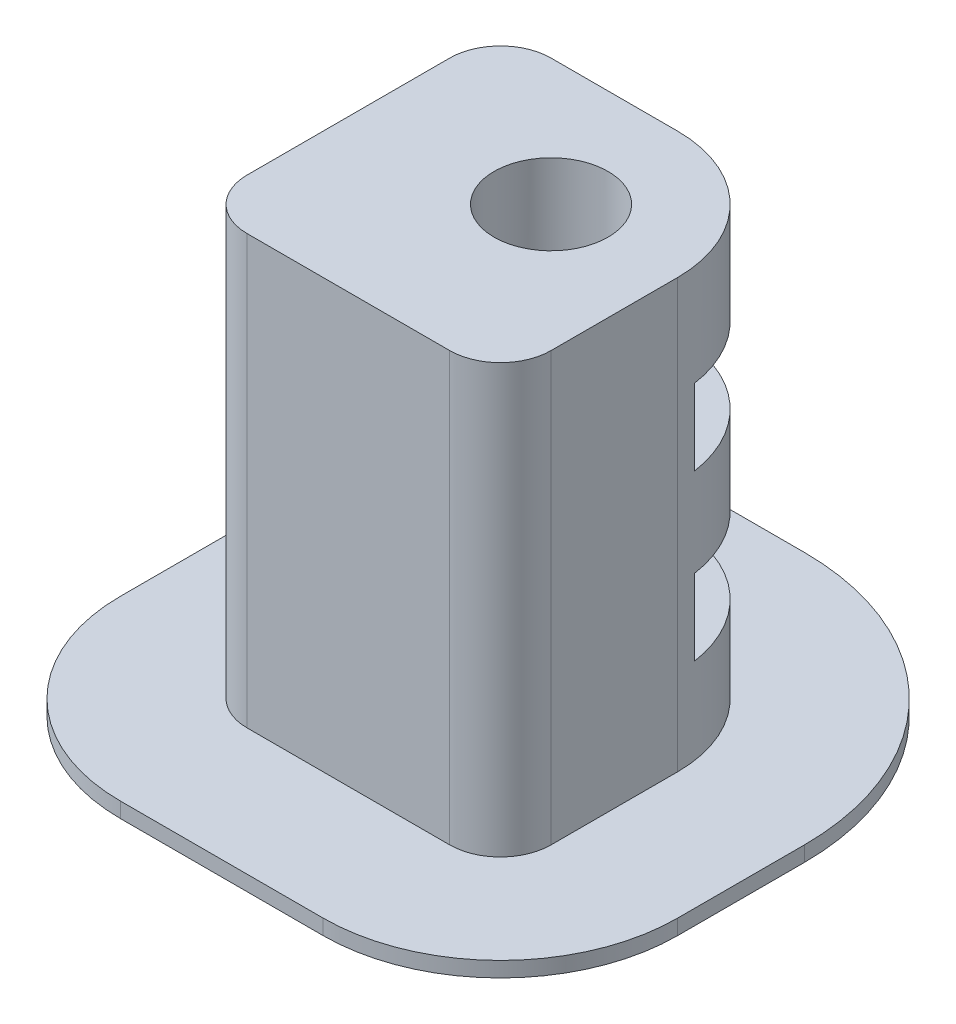
SolidWorks part; units mm, degrees
material "ABS"
ref_plane "Front Plane" through (0, 0, 0) normal (0, 0, 1) x (1, 0, 0)
ref_plane "Top Plane" through (0, 0, 0) normal (0, 1, 0) x (1, 0, 0)
ref_plane "Right Plane" through (0, 0, 0) normal (1, 0, 0) x (0, 0, -1)
sketch "Sketch1" plane through (0, 0, 0) normal (0, 1, 0) x (1, 0, 0)
  line L0 (0, 5) -> (-7, 5)
  line L1 (-7, 5) -> (-7, -7)
  line L2 (-7, -7) -> (5, -7)
  line L3 (5, -7) -> (5, 0)
  circle A0 centre (0, 0) radius 1.6
  arc A1 (5, 0) -> (0, 5) centre (0, 0) ccw
  dimension "D1" = 3.2
  dimension "D2" = 10
  dimension "D3" = 12
extrude "Boss-Extrude1" add sketch "Sketch1" along normal mid plane 17.5
fillet "Fillet1" radius 2 3 edges at (5, 0, 7) (-7, 0, 7) (-7, 0, -5)
sketch "Sketch2" plane through (0, 0, 0) normal (0, 1, 0) x (1, 0, 0)
  line L0 (-0.8966, 3.3461) -> (0.7574, 5)
  line L1 (-2.4495, -2.4495) -> (0.8966, -3.3461)
  line L2 (0.8966, -3.3461) -> (3.3461, -0.8966)
  line L3 (3.3461, -0.8966) -> (2.4495, 2.4495) construction
  line L4 (2.4495, 2.4495) -> (-0.8966, 3.3461) construction
  line L5 (-0.8966, 3.3461) -> (-3.3461, 0.8966)
  line L6 (-3.3461, 0.8966) -> (-2.4495, -2.4495)
  line L7 (0.7574, 5) -> (5, 5)
  line L8 (3.3461, -0.8966) -> (5, 0.7574)
  line L9 (5, 0.7574) -> (5, 5)
  line L11 (0, 0) -> (2.4495, 2.4495) construction
  line L12 (2.4495, 2.4495) -> (3.5355, 3.5355) construction
  line L13 (5, -5) -> (5, 0) construction
  circle A0 centre (0, 0) radius 3 construction
  arc A2 (5, 0) -> (0, 5) centre (0, 0) ccw construction
  dimension "D1" = 6
ref_plane "Plane1" through (0, 4.75, 0) normal (0, 1, 0) x (1, 0, 0)
ref_plane "Plane2" through (0, -4.75, 0) normal (0, -1, 0) x (-1, 0, 0)
extrude "Cut-Extrude1" cut sketch "Sketch2" against normal blind 3 from surface starting at plane "Plane1"
extrude "Cut-Extrude2" cut sketch "Sketch2<2>" along normal blind 3 from surface starting at plane "Plane2"
sketch "Sketch2<2>" plane through (0, 0, 0) normal (0, 1, 0) x (1, 0, 0) same geometry as "Sketch2"
sketch "Sketch3" plane through (0, 8.75, 0) normal (0, 1, 0) x (1, 0, 0)
  circle A0 centre (0, 0) radius 2.25
  dimension "D1" = 4.5
extrude "Cut-Extrude3" cut sketch "Sketch3" against normal blind 7
sketch "Sketch4" plane through (0, -8.75, 0) normal (0, -1, 0) x (1, 0, 0)
  line L26 (10, 0) -> (10, 5)
  line L27 (3, 12) -> (-5, 12)
  line L28 (-12, 5) -> (-12, -3)
  line L29 (-5, -10) -> (0, -10)
  line L30 (10, 0) -> (10, 5)
  line L31 (3, 12) -> (-5, 12)
  line L32 (-12, 5) -> (-12, -3)
  line L33 (-5, -10) -> (0, -10)
  circle A14 centre (0, 0) radius 1.6
  circle A15 centre (0, 0) radius 1.6 construction
  arc A18 (10, 5) -> (3, 12) centre (3, 5) ccw
  arc A19 (0, -10) -> (10, 0) centre (0, 0) ccw
  arc A20 (-12, -3) -> (-5, -10) centre (-5, -3) ccw
  arc A21 (-5, 12) -> (-12, 5) centre (-5, 5) ccw
  arc A22 (10, 5) -> (3, 12) centre (3, 5) ccw
  arc A23 (0, -10) -> (10, 0) centre (0, 0) ccw
  arc A24 (-12, -3) -> (-5, -10) centre (-5, -3) ccw
  arc A25 (-5, 12) -> (-12, 5) centre (-5, 5) ccw
  dimension "D1" = 5
extrude "Boss-Extrude3" add sketch "Sketch4" against normal blind 0.6
